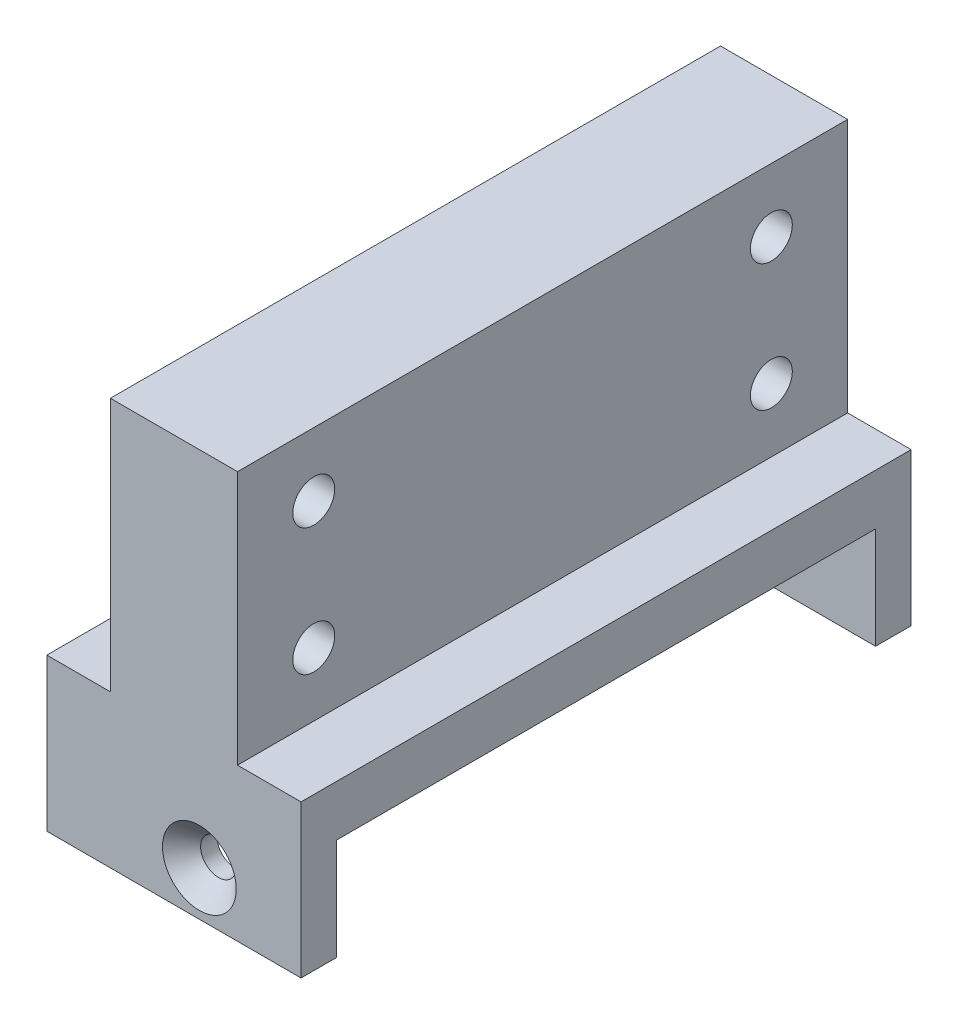
SolidWorks part; units mm, degrees
material "ABS"
ref_plane "前视基准面" through (0, 0, 0) normal (0, 0, 1) x (1, 0, 0)
ref_plane "上视基准面" through (0, 0, 0) normal (0, 1, 0) x (1, 0, 0)
ref_plane "右视基准面" through (0, 0, 0) normal (1, 0, 0) x (0, 0, -1)
sketch "草图1" plane through (0, 0, 0) normal (0, 1, 0) x (1, 0, 0)
  line L1 (-10, -24) -> (10, -24)
  line L2 (-10, -24) -> (-10, 24)
  line L3 (-10, 24) -> (10, 24)
  line L4 (10, -24) -> (10, 24)
  line L5 (-10, -24) -> (10, 24) construction
  line L6 (-10, 24) -> (10, -24) construction
  point P0 (0, 0)
  dimension "D1" = 20
  dimension "D2" = 48
extrude "凸台-拉伸2" add sketch "草图1" along normal blind 4
sketch "草图3" plane through (0, 0, 0) normal (0, -1, 0) x (1, 0, 0)
  line L0 (10, 24) -> (10, -24) construction
  line L1 (-10, 24) -> (10, 24)
  line L2 (-10, 24) -> (-10, 21)
  line L3 (-10, 21) -> (10, 21)
  line L4 (10, 24) -> (10, 21)
  line L5 (-10, 0) -> (10, 0) construction
  line L6 (-10, -24) -> (-10, 24) construction
  line L7 (-10, -21) -> (10, -21)
  line L8 (10, -24) -> (10, -21)
  line L9 (-10, -24) -> (10, -24)
  line L10 (-10, -24) -> (-10, -21)
  dimension "D1" = 3
extrude "凸台-拉伸3" add sketch "草图3" along normal blind 8
sketch "草图4" plane through (-10, 0, 0) normal (-1, 0, 0) x (0, 0, 1)
  line L0 (-24, 4) -> (24, 4) construction
  line L1 (-21, 0) -> (-9, 0)
  line L2 (-21, 0) -> (-21, 4)
  line L3 (-21, 4) -> (-9, 4)
  line L4 (-9, 0) -> (-9, 4)
  dimension "D1" = 12
extrude "凸台-拉伸4" add sketch "草图4" along normal blind 15
sketch "草图5" plane through (0, 4, 0) normal (0, 1, 0) x (1, 0, 0)
  line L0 (-10, 9) -> (-10, -24) construction
  line L1 (10, 24) -> (-10, 24) construction
  circle A0 centre (-19.1, 13) radius 1.75
  dimension "D1" = 3.5
  dimension "D2" = 9.1
  dimension "D3" = 11
extrude "切除-拉伸2" cut sketch "草图5" against normal through all
sketch "草图6" plane through (0, 0, 0) normal (0, -1, 0) x (1, 0, 0)
  line L0 (-25, -9) -> (-10, -9) construction
  line L1 (-25, -21) -> (-13, -21)
  line L2 (-25, -21) -> (-25, -9)
  line L3 (-25, -9) -> (-13, -9)
  line L4 (-13, -21) -> (-13, -9)
  circle A0 centre (-19.1, -13) radius 1.75 construction
  circle A1 centre (-19.1, -13) radius 1.75
  dimension "D1" = 12
extrude "凸台-拉伸5" add sketch "草图6" along normal blind 20
sketch "草图7" plane through (0, 4, 0) normal (0, 1, 0) x (1, 0, 0)
  line L0 (10, 24) -> (-10, 24) construction
  line L1 (-5, -24) -> (5, -24)
  line L2 (-5, -24) -> (-5, 24)
  line L3 (-5, 24) -> (5, 24)
  line L4 (5, -24) -> (5, 24)
  line L5 (-5, -24) -> (5, 24) construction
  line L6 (-5, 24) -> (5, -24) construction
  point P0 (0, 0)
  dimension "D1" = 10
extrude "凸台-拉伸6" add sketch "草图7" along normal blind 20
sketch "草图8" plane through (5, 0, 0) normal (1, 0, 0) x (0, 0, -1)
  line L0 (0, 4) -> (0, 24) construction
  line L1 (-24, 4) -> (24, 4) construction
  line L2 (-24, 24) -> (24, 24) construction
  line L3 (-24, 14) -> (24, 14) construction
  line L4 (-24, 24) -> (-24, 4) construction
  line L5 (24, 24) -> (24, 4) construction
  line L7 (-18, 9) -> (18, 9) construction
  line L8 (-18, 9) -> (-18, 19) construction
  line L9 (-18, 19) -> (18, 19) construction
  line L10 (18, 9) -> (18, 19) construction
  line L11 (-18, 9) -> (18, 19) construction
  line L12 (-18, 19) -> (18, 9) construction
  circle A2 centre (-18, 19) radius 1.65
  circle A3 centre (18, 19) radius 1.65
  circle A4 centre (18, 9) radius 1.65
  circle A5 centre (-18, 9) radius 1.65
  point P12 (0, 14)
  dimension "D1" = 36
  dimension "D3" = 3.3
  dimension "D2" = 10
extrude "切除-拉伸3" cut sketch "草图8" against normal through all
chamfer "倒角1" distance 3 angle 45 1 edges at (-10, -2, -24)
fillet "圆角2" radius 2.5 1 edges at (-13, 0, -15)
sketch "草图11" plane through (0, 0, -24) normal (0, 0, -1) x (-1, 0, 0)
  line L0 (7, -8) -> (-10, -8) construction
  line L1 (10, 4) -> (2, 4)
  line L2 (10, 4) -> (10, -8)
  line L3 (10, -8) -> (2, -8)
  line L4 (2, 4) -> (2, -8)
  dimension "D1" = 8
extrude "切除-拉伸5" cut sketch "草图11" against normal blind 3
sketch "草图12" plane through (0, 0, 24) normal (0, 0, 1) x (1, 0, 0)
  line L2 (-10, 0) -> (10, 0) construction
  line L3 (10, 4) -> (10, -8) construction
  circle A0 centre (2, -4.5) radius 1.4
  dimension "D2" = 2.8
  dimension "D1" = 4.5
  dimension "D3" = 8
extrude "切除-拉伸6" cut sketch "草图12" against normal through all
chamfer "倒角2" distance 1.5 angle 45 1 edges at (3.4, -4.5, 24)
sketch "草图14" plane through (0, -8, 0) normal (0, -1, 0) x (1, 0, 0)
  line L0 (-10, 24) -> (-10, 21) construction
  line L1 (-10, 21.2) -> (11.2744, 21.2)
  line L2 (-10, 21.2) -> (-10, -21.2)
  line L3 (-10, -21.2) -> (11.2744, -21.2)
  line L4 (11.2744, 21.2) -> (11.2744, -21.2)
  line L5 (-10, 21) -> (10, 21) construction
  line L6 (10, -21) -> (-2, -21) construction
  dimension "D1" = 0.2
  dimension "D2" = 0.2
extrude "切除-拉伸7" cut sketch "草图14" against normal blind 8
